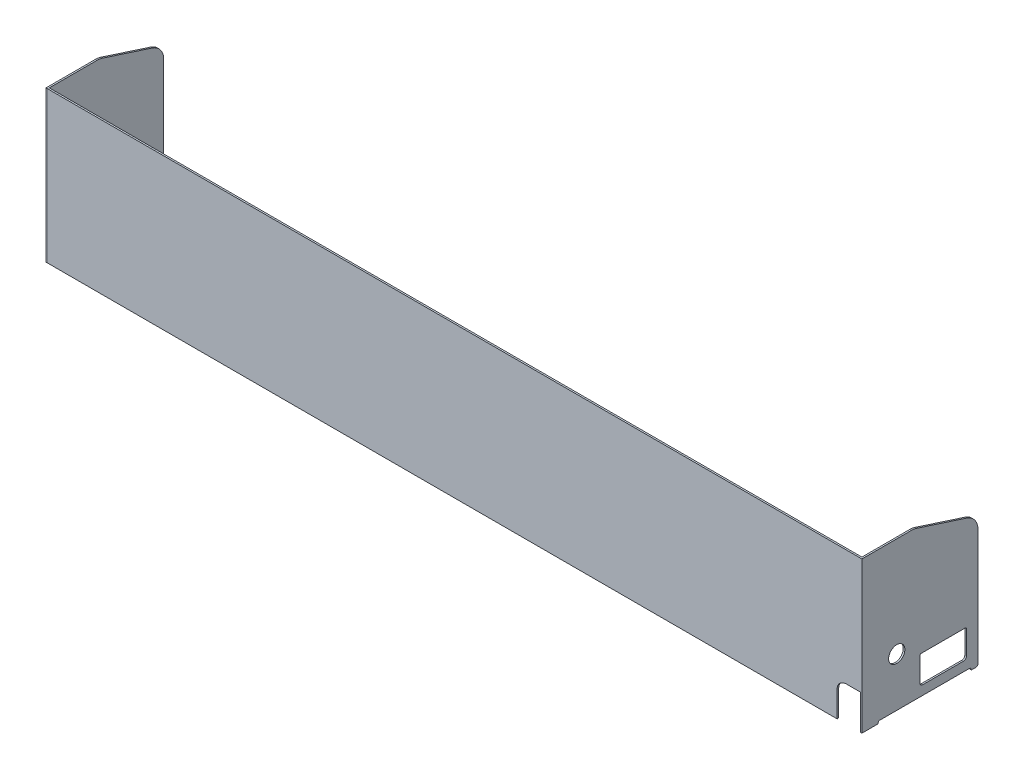
SolidWorks part; units mm, degrees
ref_plane "Front Plane" through (0, 0, 0) normal (0, 0, 1) x (1, 0, 0)
ref_plane "Top Plane" through (0, 0, 0) normal (0, 1, 0) x (1, 0, 0)
ref_plane "Right Plane" through (0, 0, 0) normal (1, 0, 0) x (0, 0, -1)
sketch "Sketch1" plane through (0, 0, 0) normal (0, 0, 1) x (1, 0, 0)
  line L0 (0, 283.3898) -> (0, -294.2373) construction
  line L1 (-518.8701, 0) -> (517.0621, 0) construction
  line L2 (175, -17.5) -> (169, -17.5)
  line L3 (-175, 32.5) -> (175, 32.5)
  line L4 (-175, 32.5) -> (-175, -32.5)
  line L5 (-175, -32.5) -> (165, -32.5)
  line L6 (175, 32.5) -> (175, -17.5)
  line L7 (165, -21.5) -> (165, -32.5)
  arc A0 (169, -17.5) -> (165, -21.5) centre (169, -21.5) ccw
  point P13 (165, -17.5)
  dimension "D5" = 4
  dimension "D1" = 350
  dimension "D2" = 65
  dimension "D3" = 10
  dimension "D4" = 15
extrude "Back Wall" add sketch "Sketch1" along normal blind 0.7
ref_plane "Right_wall Plane" through (-175, 0, 0) normal (-1, 0, 0) x (0, 0, 1)
sketch "Sketch2" plane through (-175, 0, 0) normal (-1, 0, 0) x (0, 0, 1)
  line L0 (-62.6179, 0) -> (70.933, 0) construction
  line L1 (0, 60.0387) -> (0, -42.0887) construction
  line L2 (-48.3, -32.5) -> (-46.5, -32.5)
  line L3 (-49.3, -31.5) -> (-49.3, 18.5)
  line L4 (0.7, 32.5) -> (0.7, -32.5) construction
  line L5 (0.7, 32.5) -> (-20.6433, 32.5)
  line L6 (0.7, 32.5) -> (0.7, -32.5)
  line L7 (-44.4529, 25.1607) -> (-22.7963, 32.1607)
  line L8 (-46.3, -32.3) -> (-46.3, -32.2)
  line L9 (-45.6, -31.5) -> (-7, -31.5)
  line L10 (-6.3, -32.2) -> (-6.3, -32.3)
  line L11 (-6.1, -32.5) -> (0.7, -32.5)
  line L13 (-43.8, -15.5) -> (-24.8, -15.5)
  line L14 (-44.3, -16) -> (-44.3, -26.3)
  line L15 (-43.1, -27.5) -> (-25.5, -27.5)
  line L16 (-24.3, -16) -> (-24.3, -26.3)
  arc A0 (-44.4529, 25.1607) -> (-49.3, 18.5) centre (-42.3, 18.5) ccw
  arc A1 (-20.6433, 32.5) -> (-22.7963, 32.1607) centre (-20.6433, 25.5) ccw
  arc A2 (-48.3, -32.5) -> (-49.3, -31.5) centre (-48.3, -31.5) cw
  arc A3 (-24.8, -15.5) -> (-24.3, -16) centre (-24.8, -16) cw
  arc A4 (-43.8, -15.5) -> (-44.3, -16) centre (-43.8, -16) ccw
  arc A5 (-24.3, -26.3) -> (-25.5, -27.5) centre (-25.5, -26.3) cw
  arc A6 (-43.1, -27.5) -> (-44.3, -26.3) centre (-43.1, -26.3) cw
  arc A7 (-45.6, -31.5) -> (-46.3, -32.2) centre (-45.6, -32.2) ccw
  arc A8 (-46.3, -32.3) -> (-46.5, -32.5) centre (-46.5, -32.3) cw
  arc A9 (-6.1, -32.5) -> (-6.3, -32.3) centre (-6.1, -32.3) cw
  arc A10 (-7, -31.5) -> (-6.3, -32.2) centre (-7, -32.2) cw
  circle A11 centre (-14.3, -10.5) radius 3.5
  point P16 (-49.3, 23.594)
  point P19 (-21.7465, 32.5)
  point P22 (-39.5789, -38.1792)
  point P43 (-46.3, -32.5)
  dimension "D4" = 7
  dimension "D5" = 7
  dimension "D6" = 1
  dimension "D16" = 0.5
  dimension "D17" = 1.2
  dimension "D18" = 0.7
  dimension "D19" = 0.2
  dimension "D20" = 0.2
  dimension "D21" = 0.7
  dimension "D22" = 7
  dimension "D1" = 50
  dimension "D3" = 50
  dimension "D7" = 3
  dimension "D8" = 1
  dimension "D9" = 7
  dimension "D10" = 2
  dimension "D11" = 22.7599
  dimension "D12" = 2
  dimension "D13" = 4
  dimension "D14" = 20
  dimension "D15" = 12
  dimension "D23" = 10
  dimension "0.5cm" = 5
extrude "Right Wall" add sketch "Sketch2" along normal blind 0.7 separate body
ref_plane "Left_wall Plane" through (175, 0, 0) normal (1, 0, 0) x (0, 0, -1)
ref_plane "Mid Plane" through (0, 0, 0) normal (1, 0, 0) x (0, 0, -1)
mirror "Mirror8" about plane through (0, 0, 0) normal (1, 0, 0) of "Right Wall"
